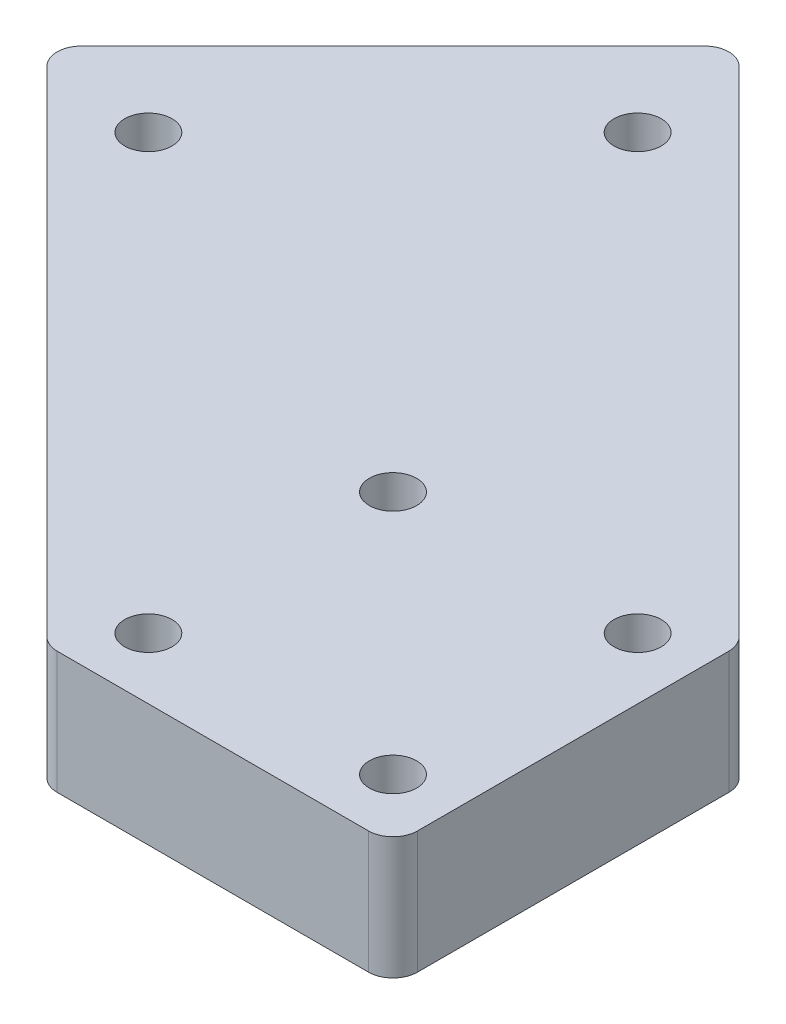
SolidWorks part; units mm, degrees
ref_plane "Front Plane" through (0, 0, 0) normal (0, 0, 1) x (1, 0, 0)
ref_plane "Top Plane" through (0, 0, 0) normal (0, 1, 0) x (1, 0, 0)
ref_plane "Right Plane" through (0, 0, 0) normal (1, 0, 0) x (0, 0, -1)
sketch "Sketch3" plane through (0, 0, 0) normal (0, 1, 0) x (1, 0, 0)
  line L1 (0, 0) -> (35.921, 0)
  line L2 (0, 0) -> (0, -35.921)
  line L3 (0, -35.921) -> (35.921, -35.921)
  line L4 (35.921, 0) -> (35.921, -35.921)
  dimension "D1" = 35.921
extrude "Boss-Extrude2" add sketch "Sketch3" along normal blind 12.7
ref_plane "Plane1" through (0, 0, 0) normal (-0.7071, 0, 0.7071) x (0.7071, 0, 0.7071)
sketch "Sketch4" plane through (0, 0, 0) normal (-0.7071, 0, 0.7071) x (0.7071, 0, 0.7071)
  line L0 (25.4, 12.7) -> (-25.4, 12.7)
  line L1 (0, 0) -> (-50.8, 0)
  line L2 (-25.4, 12.7) -> (-50.8, 12.7)
  line L3 (-50.8, 12.7) -> (-50.8, 0)
  line L4 (0, 0) -> (25.4, 0) construction
  line L5 (0, 0) -> (25.4, 0)
  line L6 (25.4, 0) -> (25.4, 12.7)
  dimension "D1" = 12.7
  dimension "D2" = 25.4
  dimension "D3" = 76.2
extrude "Boss-Extrude3" add sketch "Sketch4" along normal mid plane 50.8
hole_wizard "#8 Clearance Hole1" positions "Sketch5" profile "Sketch6" hole size "#8" standard "ANSI Inch" end condition through all
sketch "Sketch5" plane through (0, 0, 0) normal (0, -1, 0) x (-1, 0, 0)
  line L1 (-29.571, -29.571) -> (-4.171, -29.571)
  line L2 (-29.571, -29.571) -> (-29.571, -4.171)
  line L3 (-29.571, -4.171) -> (-4.171, -4.171)
  line L4 (-4.171, -29.571) -> (-4.171, -4.171)
  line L5 (-38.8909, -38.8909) -> (38.8909, 38.8909) construction
  line L6 (0, -35.921) -> (-35.921, -35.921) construction
  point P2 (-29.571, -29.571)
  point P3 (-4.171, -4.171)
  point P138 (-29.571, -4.171)
  point P139 (-4.171, -29.571)
  point P154 (0, 0)
  dimension "D1" = 6.35
  dimension "D2" = 25.4
sketch "Sketch6" plane through (29.571, 0, 29.571) normal (1, 0, 0) x (0, 0, -1)
  line L0 (0, 0) -> (0, 12.7)
  line L1 (0, 12.7) -> (2.4574, 12.7)
  line L2 (2.4574, 12.7) -> (2.4574, 0)
  line L5 (2.4574, 0) -> (0, 0)
  line L11 (0, -6.35) -> (0, 107.95) construction
  dimension "Thru Hole Dia." = 4.9149
  dimension "Thru Hole Depth" = 12.7
sketch "Sketch7" plane through (0, 12.7, 0) normal (0, 1, 0) x (1, 0, 0)
  line L0 (-38.8909, 38.8909) -> (38.8909, -38.8909) construction
  line L1 (4.171, -4.171) -> (-28.1579, 28.1579) construction
  line L2 (-40.856, 15.4598) -> (-15.4598, 40.856) construction
  circle A2 centre (4.171, -4.171) radius 2.4574 construction
  circle A3 centre (4.171, -4.171) radius 2.4574 construction
  point P4 (-15.4598, 40.856)
  point P13 (-40.856, 15.4598)
  dimension "D1" = 45.72
  dimension "D2" = 35.9156
hole_wizard "#8 Clearance Hole2" positions "Sketch8" profile "Sketch9" hole size "#8" standard "ANSI Inch" end condition through all
sketch "Sketch8" plane through (0, 12.7, 0) normal (0, 1, 0) x (1, 0, 0)
  point P0 (-40.856, 15.4598)
  point P3 (-15.4598, 40.856)
sketch "Sketch9" plane through (-40.856, 12.7, -15.4598) normal (1, 0, 0) x (0, 0, 1)
  line L0 (0, 0) -> (0, 12.7)
  line L1 (0, 12.7) -> (2.4574, 12.7)
  line L2 (2.4574, 12.7) -> (2.4574, 0)
  line L5 (2.4574, 0) -> (0, 0)
  line L11 (0, -6.35) -> (0, 107.95) construction
  dimension "Thru Hole Dia." = 4.9149
  dimension "Thru Hole Depth" = 12.7
sketch "Sketch10" plane through (0, 0, 0) normal (0, -1, 0) x (1, 0, 0)
  circle A0 centre (-40.856, -15.4598) radius 3.937
  circle A1 centre (-15.4598, -40.856) radius 3.937
  dimension "D1" = 7.874
extrude "Cut-Extrude1" cut sketch "Sketch10" against normal blind 6.35
fillet "Fillet1" radius 2.54 5 edges at (-17.9605, 6.35, -53.8815) (-53.8815, 6.35, -17.9605) (35.921, 6.35, 0) (35.921, 6.35, 35.921) (0, 6.35, 35.921)
equation "\"D1@Boss-Extrude3\"=sqr(2 )"
equation "\"D1@Sketch3\"=sqr(2)"
